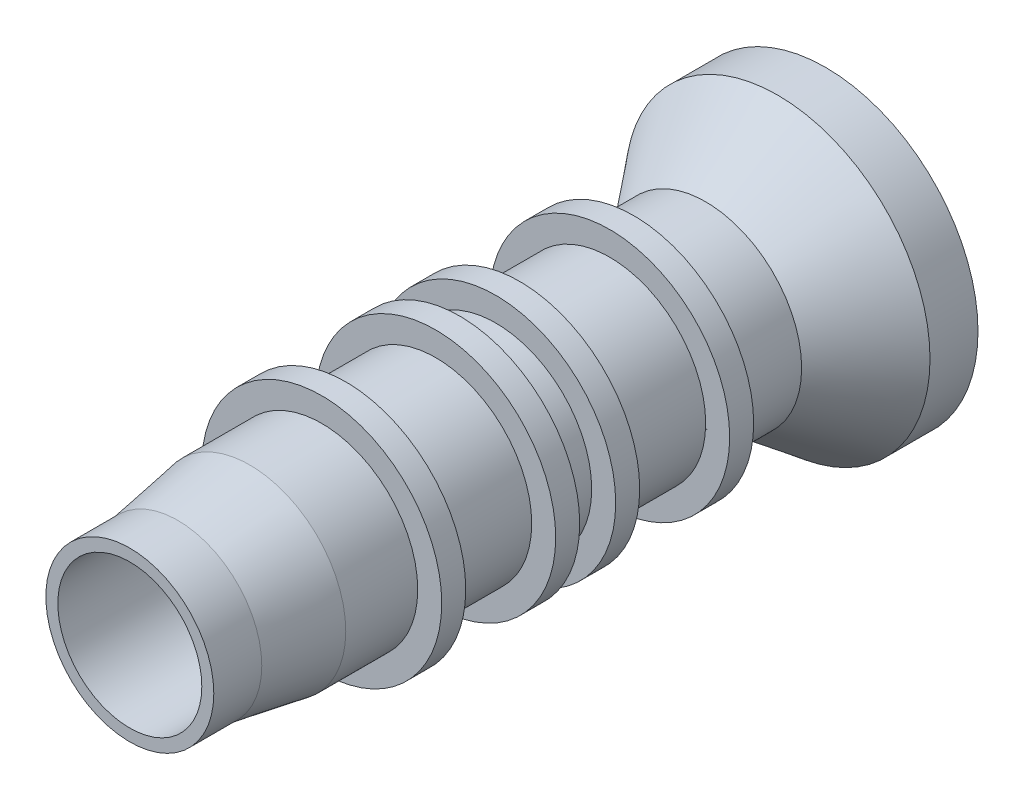
SolidWorks part; units mm, degrees
material "ABS"
ref_plane "正面" through (0, 0, 0) normal (0, 0, 1) x (1, 0, 0)
ref_plane "平面" through (0, 0, 0) normal (0, 1, 0) x (1, 0, 0)
ref_plane "右側面" through (0, 0, 0) normal (1, 0, 0) x (0, 0, -1)
sketch "ｽｹｯﾁ1" plane through (0, 0, 0) normal (0, 0, 1) x (1, 0, 0)
  circle A0 centre (0, 0) radius 4 construction
  circle A1 centre (0, 0) radius 6.35
  dimension "D1" = 8
  dimension "D2" = 12.7
ref_plane "平面1" through (0, 0, 5) normal (0, 0, 1) x (1, 0, 0)
sketch "ｽｹｯﾁ2" plane through (0, 0, 5) normal (0, 0, 1) x (1, 0, 0)
  circle A0 centre (0, 0) radius 4 construction
  circle A1 centre (0, 0) radius 4
ref_plane "平面2" through (0, 0, 29) normal (0, 0, 1) x (1, 0, 0)
ref_plane "平面3" through (0, 0, 24) normal (0, 0, 1) x (1, 0, 0)
sketch "ｽｹｯﾁ5" plane through (0, 0, 29) normal (0, 0, 1) x (1, 0, 0)
  circle A0 centre (0, 0) radius 6.35 construction
  circle A1 centre (0, 0) radius 6.35 construction
  circle A2 centre (0, 0) radius 3.5
  dimension "D1" = 7
extrude "ﾎﾞｽ - 押し出し3" add sketch "ｽｹｯﾁ2" along normal up to surface (19 mm away) contours A1 up to plane "平面3"
extrude "ﾎﾞｽ - 押し出し4" add sketch "ｽｹｯﾁ1" along normal blind 2 separate body
extrude "ﾎﾞｽ - 押し出し5" add sketch "ｽｹｯﾁ5" against normal blind 2
loft "ﾛﾌﾄ1" add section face at (6.35, 0, 2) section face at (4, 0, 5) connector at (-0.1759, 6.3476, 2) connector at (-0.0849, 3.9991, 5)
loft "ﾛﾌﾄ2" add section face at (4, 0, 24) section face at (3.5, 0, 27) connector at (-0.0856, 3.9991, 24) connector at (-0.0751, 3.4992, 27)
ref_plane "平面5" through (0, 0, 14.5) normal (0, 0, 1) x (1, 0, 0)
ref_plane "平面6" through (0, 0, 15.25) normal (0, 0, 1) x (1, 0, 0)
sketch "ｽｹｯﾁ9" plane through (0, 0, 15.25) normal (0, 0, 1) x (1, 0, 0)
  circle A0 centre (0, 0) radius 5
  dimension "D1" = 10
extrude "ﾎﾞｽ - 押し出し6" add sketch "ｽｹｯﾁ9" along normal blind 1
ref_plane "平面7" through (0, 0, 20) normal (0, 0, 1) x (1, 0, 0)
sketch "ｽｹｯﾁ10" plane through (0, 0, 20) normal (0, 0, 1) x (1, 0, 0)
  circle A1 centre (0, 0) radius 5
  circle A2 centre (0, 0) radius 5
  dimension "D1" = 0
extrude "ﾎﾞｽ - 押し出し7" add sketch "ｽｹｯﾁ10" along normal blind 1
mirror "ﾐﾗｰ3" about plane through (0, 0, 14.5) normal (0, 0, 1) of "ﾎﾞｽ - 押し出し7", "ﾎﾞｽ - 押し出し6"
sketch "ｽｹｯﾁ6" plane through (0, 0, 0) normal (0, 0, -1) x (-1, 0, 0)
  circle A0 centre (0, 0) radius 2.75
  dimension "D1" = 5.5
extrude "ｶｯﾄ - 押し出し1" cut sketch "ｽｹｯﾁ6" against normal blind 3
sketch "ｽｹｯﾁ7" plane through (0, 0, 3) normal (0, 0, -1) x (-1, 0, 0)
  circle A0 centre (0, 0) radius 1.8
  dimension "D1" = 3.6
extrude "ｶｯﾄ - 押し出し2" cut sketch "ｽｹｯﾁ7" against normal through all
sketch "ｽｹｯﾁ8" plane through (0, 0, 29) normal (0, 0, 1) x (1, 0, 0)
  circle A0 centre (0, 0) radius 3
  dimension "D1" = 6
extrude "ｶｯﾄ - 押し出し3" cut sketch "ｽｹｯﾁ8" against normal offset from surface (23 mm away) 3 up to face at (-1.8, 0, 3)
ref_plane "平面9" through (-4, 0, 0) normal (-1, 0, 0) x (0, 0, 1)
sketch "ｽｹｯﾁ11" plane through (-4, 0, 0) normal (-1, 0, 0) x (0, 0, 1)
  line L0 (0, 0) -> (29, 0) construction
  line L1 (29, -6.9851) -> (29, 6.9851) construction
  line L3 (16.25, 1) -> (18.25, 1)
  line L4 (16.25, 1) -> (16.25, -1)
  line L5 (16.25, -1) -> (18.25, -1)
  line L6 (18.25, 1) -> (18.25, -1)
  line L7 (16.25, 1) -> (18.25, -1) construction
  line L8 (16.25, -1) -> (18.25, 1) construction
  line L10 (13.75, 1) -> (15.25, 1)
  line L11 (13.75, 1) -> (13.75, -1)
  line L12 (13.75, -1) -> (15.25, -1)
  line L13 (15.25, 1) -> (15.25, -1)
  line L14 (13.75, 1) -> (15.25, -1) construction
  line L15 (13.75, -1) -> (15.25, 1) construction
  line L17 (9, 1) -> (11, 1)
  line L18 (9, 1) -> (9, -1)
  line L19 (9, -1) -> (11, -1)
  line L20 (11, 1) -> (11, -1)
  line L21 (9, 1) -> (11, -1) construction
  line L22 (9, -1) -> (11, 1) construction
  line L23 (9, -4) -> (9, 4) construction
  line L24 (13.75, -5) -> (13.75, 5) construction
  line L25 (16.25, -5) -> (16.25, 5) construction
  point P5 (17.25, 0)
  point P12 (14.5, 0)
  point P19 (10, 0)
  point P26 (0, 0)
  dimension "D1" = 2
  dimension "D2" = 2
  dimension "D3" = 1.5
  dimension "D4" = 2
extrude "ｶｯﾄ - 押し出し4" cut sketch "ｽｹｯﾁ11" against normal up to next
sketch "ｽｹｯﾁ12" plane through (0, 0, 0) normal (0, 0, -1) x (-1, 0, 0)
  line L0 (0, 0) -> (0, 2.75) construction
  line L1 (0, 0) -> (0.3745, 2.7244) construction
  line L2 (0, 0) -> (0.7419, 2.648) construction
  line L3 (0, 0) -> (1.0956, 2.5223) construction
  line L4 (0, 0) -> (1.4289, 2.3497) construction
  line L5 (0, 0) -> (1.7355, 2.1332) construction
  line L6 (0, 0) -> (2.0098, 1.877) construction
  line L7 (0, 0) -> (2.2467, 1.5859) construction
  line L8 (0, 0) -> (2.4417, 1.2652) construction
  line L9 (0, 0) -> (2.5912, 0.9209) construction
  line L10 (0, 0) -> (2.6925, 0.5595) construction
  line L11 (0, 0) -> (2.7436, 0.1877) construction
  line L12 (0, 0) -> (2.7436, -0.1877) construction
  line L13 (0, 0) -> (2.6925, -0.5595) construction
  line L14 (0, 0) -> (2.5912, -0.9209) construction
  line L15 (0, 0) -> (2.4417, -1.2652) construction
  line L16 (0, 0) -> (2.2467, -1.5859) construction
  line L17 (0, 0) -> (2.0098, -1.877) construction
  line L18 (0, 0) -> (1.7355, -2.1332) construction
  line L19 (0, 0) -> (1.4289, -2.3497) construction
  line L20 (0, 0) -> (1.0956, -2.5223) construction
  line L21 (0, 0) -> (0.7419, -2.648) construction
  line L22 (0, 0) -> (0.3745, -2.7244) construction
  line L23 (0, 0) -> (0, -2.75) construction
  line L24 (0, 0) -> (-0.3745, -2.7244) construction
  line L25 (0, 0) -> (-0.7419, -2.648) construction
  line L26 (0, 0) -> (-1.0956, -2.5223) construction
  line L27 (0, 0) -> (-1.4289, -2.3497) construction
  line L28 (0, 0) -> (-1.7355, -2.1332) construction
  line L29 (0, 0) -> (-2.0098, -1.877) construction
  line L30 (0, 0) -> (-2.2467, -1.5859) construction
  line L31 (0, 0) -> (-2.4417, -1.2652) construction
  line L32 (0, 0) -> (-2.5912, -0.9209) construction
  line L33 (0, 0) -> (-2.6925, -0.5595) construction
  line L34 (0, 0) -> (-2.7436, -0.1877) construction
  line L35 (0, 0) -> (-2.7436, 0.1877) construction
  line L36 (0, 0) -> (-2.6925, 0.5595) construction
  line L37 (0, 0) -> (-2.5912, 0.9209) construction
  line L38 (0, 0) -> (-2.4417, 1.2652) construction
  line L39 (0, 0) -> (-2.2467, 1.5859) construction
  line L40 (0, 0) -> (-2.0098, 1.877) construction
  line L41 (0, 0) -> (-1.7355, 2.1332) construction
  line L42 (0, 0) -> (-1.4289, 2.3497) construction
  line L43 (0, 0) -> (-1.0956, 2.5223) construction
  line L44 (0, 0) -> (-0.7419, 2.648) construction
  line L45 (0, 0) -> (-0.3745, 2.7244) construction
  line L46 (0, 0) -> (0.2081, 3.0429) construction
  line L47 (0.2081, 3.0429) -> (-0.0626, 2.7493)
  line L48 (-0.0626, 2.7493) -> (0, 0) construction
  line L49 (0, 0) -> (0.4364, 2.7152) construction
  line L50 (0.4364, 2.7152) -> (0.2081, 3.0429)
  line L51 (1.0214, 2.8739) -> (0.6815, 2.6642)
  line L52 (1.1527, 2.4967) -> (1.0214, 2.8739)
  line L53 (1.7589, 2.4918) -> (1.375, 2.3816)
  line L54 (1.7836, 2.0931) -> (1.7589, 2.4918)
  line L55 (2.3659, 1.9248) -> (1.9666, 1.9223)
  line L56 (2.2822, 1.5343) -> (2.3659, 1.9248)
  line L57 (2.7975, 1.2151) -> (2.4123, 1.3204)
  line L58 (2.6115, 0.8617) -> (2.7975, 1.2151)
  line L59 (3.0216, 0.4153) -> (2.679, 0.6206)
  line L60 (2.7472, 0.1252) -> (3.0216, 0.4153)
  line L61 (3.0216, -0.4153) -> (2.7472, -0.1252)
  line L62 (2.679, -0.6206) -> (3.0216, -0.4153)
  line L63 (2.7975, -1.2151) -> (2.6115, -0.8617)
  line L64 (2.4123, -1.3204) -> (2.7975, -1.2151)
  line L65 (2.3659, -1.9248) -> (2.2822, -1.5343)
  line L66 (1.9666, -1.9223) -> (2.3659, -1.9248)
  line L67 (1.7589, -2.4918) -> (1.7836, -2.0931)
  line L68 (1.375, -2.3816) -> (1.7589, -2.4918)
  line L69 (1.0214, -2.8739) -> (1.1527, -2.4967)
  line L70 (0.6815, -2.6642) -> (1.0214, -2.8739)
  line L71 (0.2081, -3.0429) -> (0.4364, -2.7152)
  line L72 (-0.0626, -2.7493) -> (0.2081, -3.0429)
  line L73 (-0.6205, -2.9862) -> (-0.3123, -2.7322)
  line L74 (-0.802, -2.6304) -> (-0.6205, -2.9862)
  line L75 (-1.4032, -2.708) -> (-1.0379, -2.5466)
  line L76 (-1.482, -2.3165) -> (-1.4032, -2.708)
  line L77 (-2.0818, -2.229) -> (-1.6865, -2.1722)
  line L78 (-2.052, -1.8308) -> (-2.0818, -2.229)
  line L79 (-2.606, -1.5847) -> (-2.21, -1.6366)
  line L80 (-2.4699, -1.2093) -> (-2.606, -1.5847)
  line L81 (-2.9369, -0.8229) -> (-2.5696, -0.9797)
  line L82 (-2.7045, -0.4981) -> (-2.9369, -0.8229)
  line L83 (-3.05, 0) -> (-2.7386, -0.2501)
  line L84 (-2.7386, 0.2501) -> (-3.05, 0)
  line L85 (-2.9369, 0.8229) -> (-2.7045, 0.4981)
  line L86 (-2.5696, 0.9797) -> (-2.9369, 0.8229)
  line L87 (-2.606, 1.5847) -> (-2.4699, 1.2093)
  line L88 (-2.21, 1.6366) -> (-2.606, 1.5847)
  line L89 (-2.0818, 2.229) -> (-2.052, 1.8308)
  line L90 (-1.6865, 2.1722) -> (-2.0818, 2.229)
  line L91 (-1.4032, 2.708) -> (-1.482, 2.3165)
  line L92 (-1.0379, 2.5466) -> (-1.4032, 2.708)
  line L93 (-0.6205, 2.9862) -> (-0.802, 2.6304)
  line L94 (-0.3123, 2.7322) -> (-0.6205, 2.9862)
  circle A0 centre (0, 0) radius 2.75 construction
  circle A1 centre (0, 0) radius 3.05 construction
  arc A2 (0, 2.75) -> (0.3745, 2.7244) centre (0, 0) cw construction
  circle A3 centre (0, 0) radius 2.75 construction
  arc A4 (-0.0626, 2.7493) -> (0.4364, 2.7152) centre (0, 0) cw
  arc A5 (0.6815, 2.6642) -> (1.1527, 2.4967) centre (0, 0) cw
  arc A6 (1.375, 2.3816) -> (1.7836, 2.0931) centre (0, 0) cw
  arc A7 (1.9666, 1.9223) -> (2.2822, 1.5343) centre (0, 0) cw
  arc A8 (2.4123, 1.3204) -> (2.6115, 0.8617) centre (0, 0) cw
  arc A9 (2.679, 0.6206) -> (2.7472, 0.1252) centre (0, 0) cw
  arc A10 (2.7472, -0.1252) -> (2.679, -0.6206) centre (0, 0) cw
  arc A11 (2.6115, -0.8617) -> (2.4123, -1.3204) centre (0, 0) cw
  arc A12 (2.2822, -1.5343) -> (1.9666, -1.9223) centre (0, 0) cw
  arc A13 (1.7836, -2.0931) -> (1.375, -2.3816) centre (0, 0) cw
  arc A14 (1.1527, -2.4967) -> (0.6815, -2.6642) centre (0, 0) cw
  arc A15 (0.4364, -2.7152) -> (-0.0626, -2.7493) centre (0, 0) cw
  arc A16 (-0.3123, -2.7322) -> (-0.802, -2.6304) centre (0, 0) cw
  arc A17 (-1.0379, -2.5466) -> (-1.482, -2.3165) centre (0, 0) cw
  arc A18 (-1.6865, -2.1722) -> (-2.052, -1.8308) centre (0, 0) cw
  arc A19 (-2.21, -1.6366) -> (-2.4699, -1.2093) centre (0, 0) cw
  arc A20 (-2.5696, -0.9797) -> (-2.7045, -0.4981) centre (0, 0) cw
  arc A21 (-2.7386, -0.2501) -> (-2.7386, 0.2501) centre (0, 0) cw
  arc A22 (-2.7045, 0.4981) -> (-2.5696, 0.9797) centre (0, 0) cw
  arc A23 (-2.4699, 1.2093) -> (-2.21, 1.6366) centre (0, 0) cw
  arc A24 (-2.052, 1.8308) -> (-1.6865, 2.1722) centre (0, 0) cw
  arc A25 (-1.482, 2.3165) -> (-1.0379, 2.5466) centre (0, 0) cw
  arc A26 (-0.802, 2.6304) -> (-0.3123, 2.7322) centre (0, 0) cw
  point P53 (0, 0)
  point P54 (0.1877, 2.7436)
  point P56 (0.1877, 2.7436)
  point P129 (0, 0)
  dimension "D2" = 6.1
  dimension "D3" = 10.435
  dimension "D1" = 46
  dimension "D4" = 23
extrude "ｶｯﾄ - 押し出し5" cut sketch "ｽｹｯﾁ12" against normal up to surface (3 mm away) up to face at (-1.8, 0, 3)
equation "\"D3@ｽｹｯﾁ12\"=360/23*2/3"
